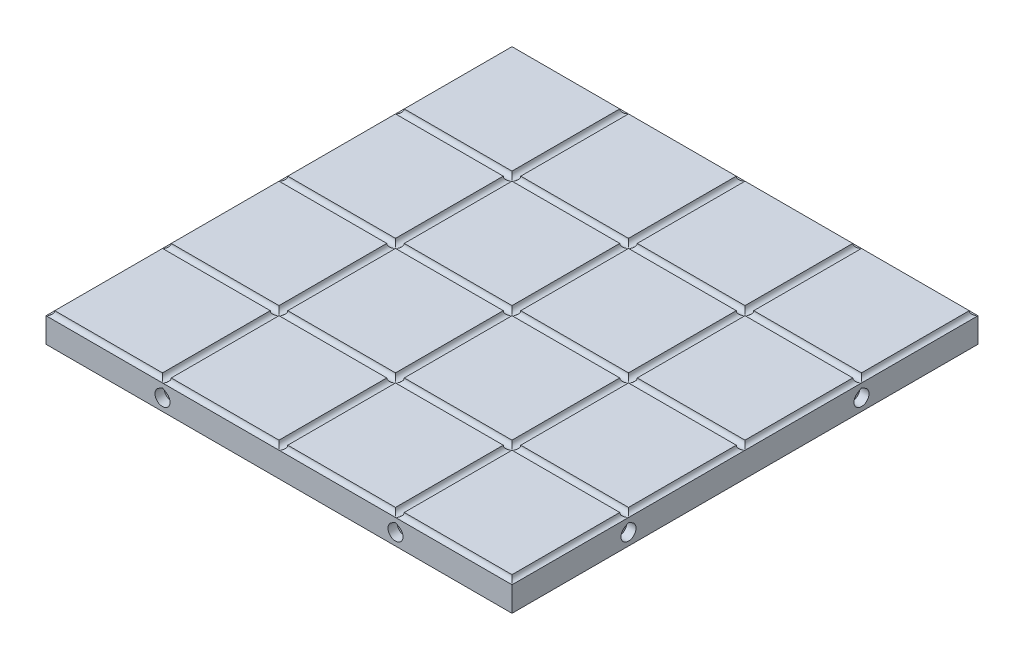
SolidWorks part; units mm, degrees
ref_plane "Спереди" through (0, 0, 0) normal (0, 0, 1) x (1, 0, 0)
ref_plane "Сверху" through (0, 0, 0) normal (0, 1, 0) x (1, 0, 0)
ref_plane "Справа" through (0, 0, 0) normal (1, 0, 0) x (0, 0, -1)
sketch "Эскиз1" plane through (0, 0, 0) normal (0, 1, 0) x (1, 0, 0)
  line L1 (80, -80) -> (-80, -80)
  line L2 (80, -80) -> (80, 80)
  line L3 (80, 80) -> (-80, 80)
  line L4 (-80, -80) -> (-80, 80)
  line L5 (0, 80) -> (0, -80) construction
  line L6 (80, 0) -> (-80, 0) construction
  point P0 (0, 0)
  dimension "D1" = 160
extrude "Бобышка-Вытянуть1" add sketch "Эскиз1" against normal blind 10
sketch "Эскиз2" plane through (0, 0, 0) normal (0, 1, 0) x (1, 0, 0)
  line L0 (-80, 80) -> (-80, -80)
sweep "Вырез-По траектории1" cut path "Эскиз2" circular profile diameter 3 parameters "D3"=3
pattern_linear "Линейный массив1" count 5 spacing 40 along (1, 0, 0) of "Вырез-По траектории1"
sketch "Эскиз180" plane through (0, 0, 0) normal (0, 1, 0) x (1, 0, 0)
  line L0 (-80, -80) -> (80, -80)
sweep "Вырез-По траектории2" cut path "Эскиз180" circular profile diameter 3 parameters "D3"=3
pattern_linear "Линейный массив2" count 5 spacing 40 along (1, 0, 0) count 5 spacing 40 along (0, 0, -1) of "Вырез-По траектории2"
sketch "Эскиз181" plane through (0, 0, 80) normal (0, 0, 1) x (1, 0, 0)
  line L0 (0, 22.1626) -> (0, -39.4564) construction
  line L3 (-40, -1.5) -> (-40, -10) construction
  line L4 (-80, -10) -> (80, -10) construction
  line L5 (40, -2.9758) -> (38.7125, -3.7192)
  line L8 (40, -2.9758) -> (41.2875, -3.7192)
  line L9 (-80, -10) -> (-80, -1.5) construction
  line L10 (-48.6563, -5.75) -> (-30.5924, -5.75) construction
  line L13 (-40, -2.9758) -> (-41.2875, -3.7192)
  line L14 (-80, -1.5) -> (-40, -1.5) construction
  line L15 (-40, -2.9758) -> (-38.7125, -3.7192)
  circle A2 centre (-40, -5.9492) radius 2.575
  circle A3 centre (40, -5.9492) radius 2.575
  point P22 (-40, -8.5242)
  dimension "D1" = 5.15
  dimension "D6" = 40
  dimension "D2" = 60
  dimension "D3" = 1.4758
  dimension "D4" = 1.4758
  dimension "D5" = 120
extrude "Вырез-Вытянуть1" cut sketch "Эскиз181" against normal blind 3.15 contours A2 | A2 L15 L13 | A3 | L5 A3 L8
pattern_circular "Круговой массив1" count 4 over 360 about axis through (0, -10, 0) along (0, -1, 0) of "Вырез-Вытянуть1" other way count 4
